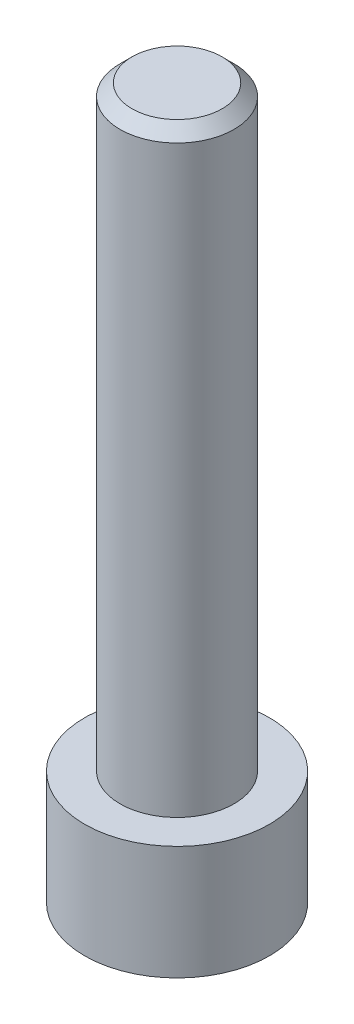
SolidWorks part; units mm, degrees
ref_plane "Front Plane" through (0, 0, 0) normal (0, 0, 1) x (1, 0, 0)
ref_plane "Top Plane" through (0, 0, 0) normal (0, 1, 0) x (1, 0, 0)
ref_plane "Right Plane" through (0, 0, 0) normal (1, 0, 0) x (0, 0, -1)
sketch "Sketch1" plane through (0, 0, 0) normal (0, 1, 0) x (1, 0, 0)
  line L1 (4.4745, 0) -> (2.2372, 3.875) construction
  line L2 (2.2372, 3.875) -> (-2.2372, 3.875) construction
  line L3 (-2.2372, 3.875) -> (-4.4745, 0) construction
  line L4 (-4.4745, 0) -> (-2.2372, -3.875) construction
  line L5 (-2.2372, -3.875) -> (2.2372, -3.875) construction
  line L6 (2.2372, -3.875) -> (4.4745, 0) construction
  circle A0 centre (0, 0) radius 3.875
  dimension "D1" = 7.75
extrude "Boss-Extrude1" add sketch "Sketch1" along normal blind 29.78
sketch "Sketch2" plane through (0, 29.78, 0) normal (0, 1, 0) x (1, 0, 0)
  circle A0 centre (0, 0) radius 2.39
  dimension "D1" = 4.78
extrude "Cut-Extrude1" cut sketch "Sketch2" against normal blind 25 flip side to cut
ref_axis "Axis1" through (0, 4.78, 0) along (0, 1, 0)
chamfer "Chamfer1" distance 0.5 angle 45 1 edges at (0, 29.78, 2.39)
sketch "Sketch5" plane through (0, 29.78, 0) normal (0, 1, 0) x (1, 0, 0)
  circle A0 centre (0, 0) radius 2.39
  dimension "D1" = 4.78
curve "Helix/Spiral1" pitch 0.7 height 25 turns 35.7143
ref_plane "Plane1" through (0, 29.78, 2.39) normal (-0.9989, -0.0466, 0) x (0, 0, 1)
sketch "Sketch8" plane through (0, 0, 0) normal (0, -1, 0) x (1, 0, 0)
  line L1 (2.6443, 0) -> (1.3221, 2.29)
  line L2 (1.3221, 2.29) -> (-1.3221, 2.29)
  line L3 (-1.3221, 2.29) -> (-2.6443, 0)
  line L4 (-2.6443, 0) -> (-1.3221, -2.29)
  line L5 (-1.3221, -2.29) -> (1.3221, -2.29)
  line L6 (1.3221, -2.29) -> (2.6443, 0)
  circle A0 centre (0, 0) radius 2.29 construction
  dimension "D1" = 4.58
extrude "Cut-Extrude2" cut sketch "Sketch8" against normal blind 3.36
